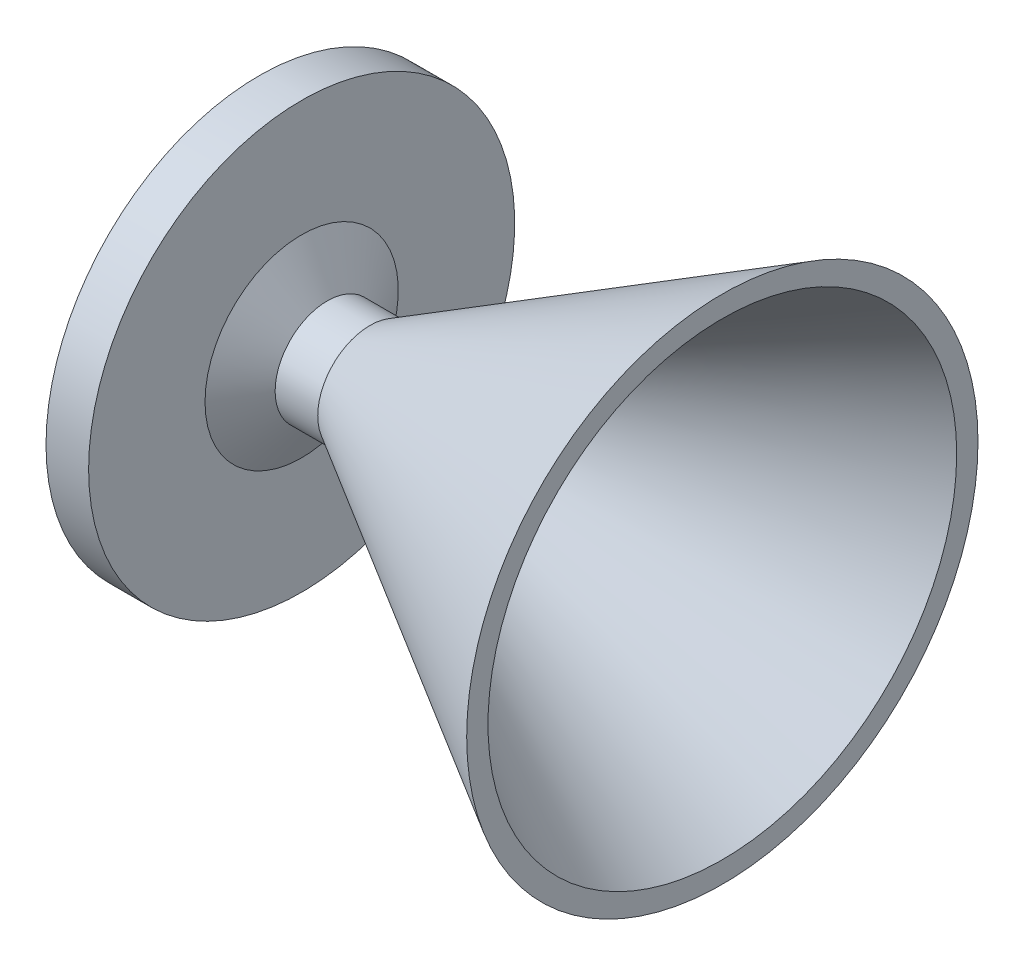
SolidWorks part; units mm, degrees
material "C (Graphite)"
ref_plane "Front Plane" through (0, 0, 0) normal (0, 0, 1) x (1, 0, 0)
ref_plane "Top Plane" through (0, 0, 0) normal (0, 1, 0) x (1, 0, 0)
ref_plane "Right Plane" through (0, 0, 0) normal (1, 0, 0) x (0, 0, -1)
sketch "Sketch1" plane through (0, 0, 0) normal (0, 0, 1) x (1, 0, 0)
  line L0 (0, 0) -> (215.3765, 0) construction
  line L1 (0, 0) -> (0, 93.6004) construction
  line L2 (0, 15.5575) -> (105.0359, 76.2)
  line L3 (0, 7.9375) -> (105.0359, 69.85)
  line L4 (105.0359, 76.2) -> (105.0359, 69.85)
  line L9 (0, 15.5575) -> (-12.7, 15.5575)
  line L10 (0, 7.9375) -> (-12.7, 7.9375)
  line L14 (-12.7, 15.5575) -> (-20.3473, 28.803)
  line L22 (-12.7, 7.9375) -> (-33.0473, 44.45)
  line L23 (-33.0473, 50.8) -> (-33.0473, 44.45)
  line L24 (-33.0473, 50.8) -> (-33.0473, 63.5)
  line L25 (-33.0473, 63.5) -> (-20.3473, 63.5)
  line L26 (-20.3473, 63.5) -> (-20.3473, 28.803)
  dimension "D1" = 6.35
  dimension "D2" = 7.62
  dimension "D3" = 7.9375
  dimension "D4" = 6.35
  dimension "D5" = 12.7
  dimension "D6" = 76.2
  dimension "D7" = 12.7
  dimension "D8" = 30
  dimension "D9" = 60
  dimension "D10" = 50.8
  dimension "D11" = 12.7
  dimension "D12" = 12.7
revolve "Revolve1" add sketch "Sketch1" angle 360 about L0
